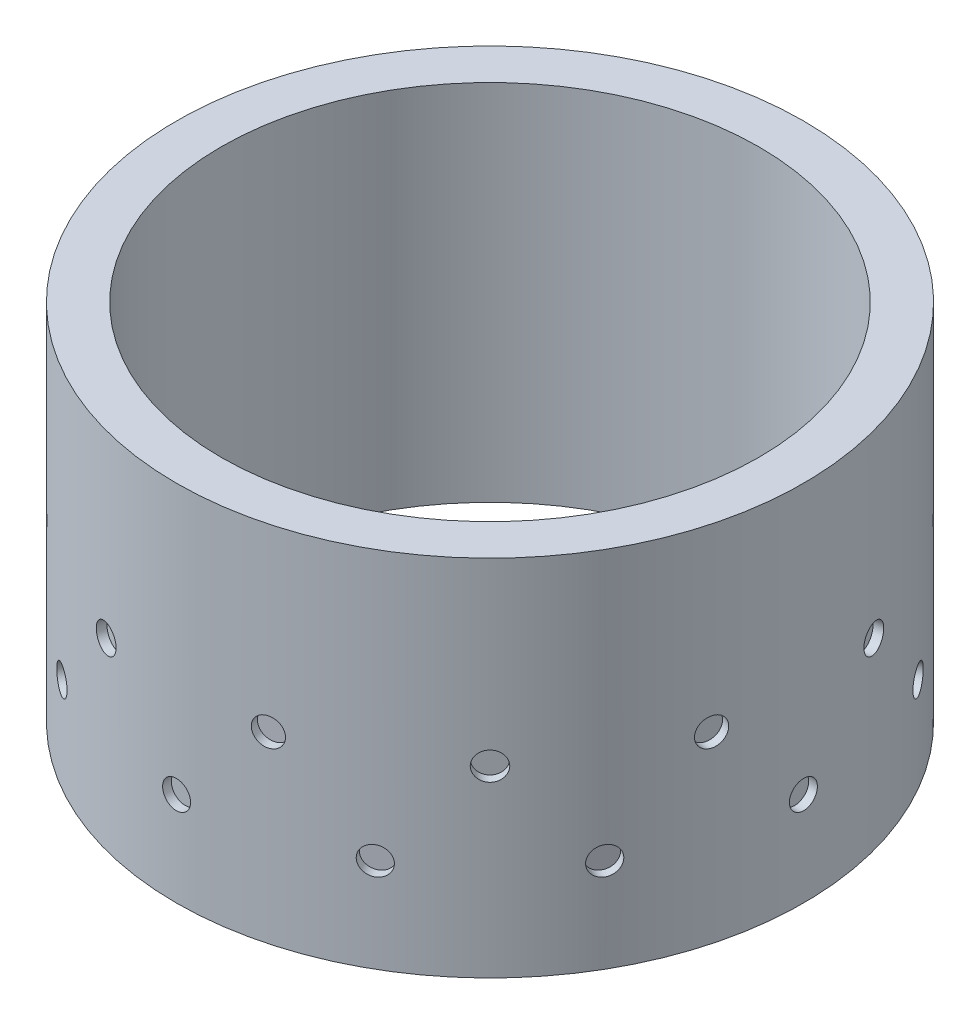
SolidWorks part; units mm, degrees
ref_plane "Front Plane" through (0, 0, 0) normal (0, 0, 1) x (1, 0, 0)
ref_plane "Top Plane" through (0, 0, 0) normal (0, 1, 0) x (1, 0, 0)
ref_plane "Right Plane" through (0, 0, 0) normal (1, 0, 0) x (0, 0, -1)
sketch "Sketch1" plane through (0, 0, 0) normal (0, 1, 0) x (1, 0, 0)
  circle A0 centre (0, 0) radius 76.327
  circle A1 centre (0, 0) radius 89.027
  dimension "D1" = 152.654
  dimension "D2" = 178.054
extrude "Boss-Extrude1" add sketch "Sketch1" along normal blind 103.1875
sketch "Sketch2" plane through (0, 0, 0) normal (0, -1, 0) x (1, 0, 0)
  line L0 (0, 0) -> (0, -89.027)
  circle A0 centre (0, 0) radius 89.027 construction
ref_plane "Plane1" through (0, 0, -89.027) normal (0, 0, -1) x (-1, 0, 0)
sketch "Sketch3" plane through (0, 0, -89.027) normal (0, 0, -1) x (-1, 0, 0)
  line L0 (0, 0) -> (0, 26.67) construction
  circle A0 centre (0, 26.67) radius 3.9688
  dimension "D1" = 7.9375
extrude "Cut-Extrude1" cut sketch "Sketch3" against normal blind 2.54
pattern_circular "CirPattern1" count 12 over 360 about axis through (0, 103.1875, 0) along (0, -1, 0) of "Cut-Extrude1" reverse direction yes
ref_plane "Plane2" through (-23.0419, 0, 85.9935) normal (-0.2588, 0, 0.9659) x (0, -1, 0)
sketch "Sketch4" plane through (-23.0419, 0, 85.9935) normal (-0.2588, 0, 0.9659) x (0, -1, 0)
  line L0 (0, 0) -> (-52.07, 0) construction
  circle A0 centre (-52.07, 0) radius 3.9687
  dimension "D2" = 7.9375
  dimension "D1" = 52.07
extrude "Cut-Extrude2" cut sketch "Sketch4" against normal blind 2.54 contours A0
pattern_circular "CirPattern2" count 12 over 360 about axis through (0, 103.1875, 0) along (0, -1, 0) of "Cut-Extrude2" reverse direction yes
